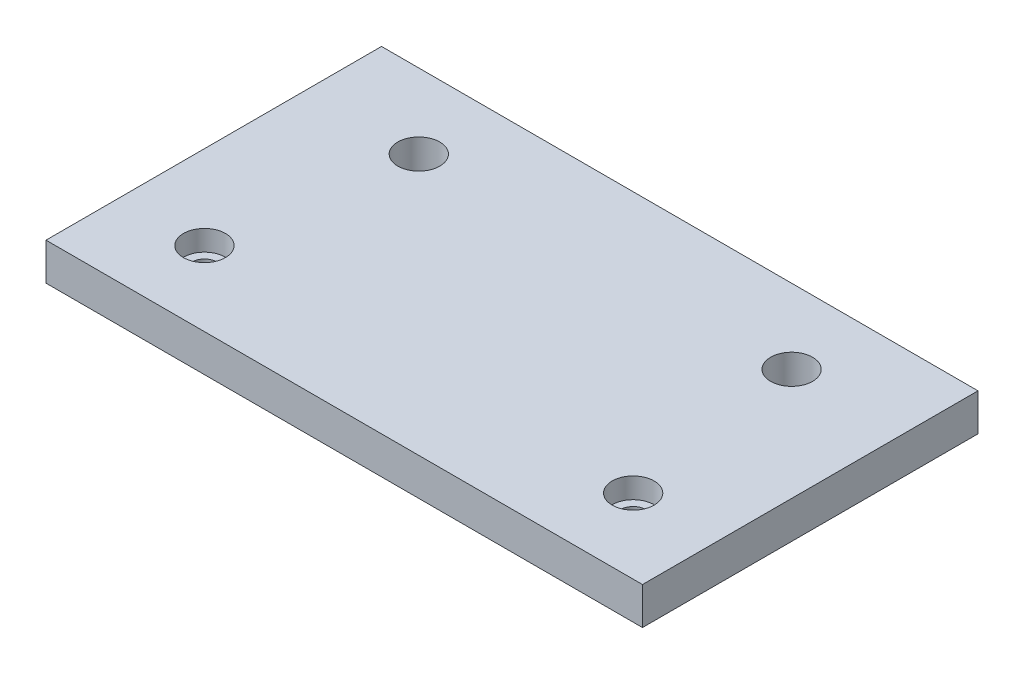
SolidWorks part; units mm, degrees
material "6061 Alloy"
ref_plane "Front Plane" through (0, 0, 0) normal (0, 0, 1) x (1, 0, 0)
ref_plane "Top Plane" through (0, 0, 0) normal (0, 1, 0) x (1, 0, 0)
ref_plane "Right Plane" through (0, 0, 0) normal (1, 0, 0) x (0, 0, -1)
sketch "Sketch1" plane through (0, 0, 0) normal (0, 1, 0) x (1, 0, 0)
  line L1 (0, 0) -> (101.6, 0)
  line L2 (0, 0) -> (0, -57.15)
  line L3 (0, -57.15) -> (101.6, -57.15)
  line L4 (101.6, 0) -> (101.6, -57.15)
  dimension "D1" = 101.6
  dimension "D2" = 57.15
extrude "Boss-Extrude1" add sketch "Sketch1" along normal blind 6.35
sketch "Sketch2" plane through (0, 6.35, 0) normal (0, 1, 0) x (1, 0, 0)
  line L0 (50.8, 0) -> (50.8, -57.15) construction
  line L1 (101.6, 0) -> (0, 0) construction
  line L2 (0, -57.15) -> (101.6, -57.15) construction
  line L3 (0, -28.575) -> (101.6, -28.575) construction
  line L4 (0, 0) -> (0, -57.15) construction
  line L5 (101.6, -57.15) -> (101.6, 0) construction
  point P12 (14.2875, -44.45)
  point P13 (87.3125, -44.45)
  point P14 (19.05, -12.7)
  point P15 (82.55, -12.7)
  dimension "D1" = 36.5125
  dimension "D2" = 12.7
  dimension "D3" = 31.75
  dimension "D4" = 31.75
hole_wizard "CBORE for #6 Socket Head Cap Screw1" positions "Sketch3" profile "Sketch4" counterbore size "#6" standard "ANSI Inch" end condition up to next
sketch "Sketch3" plane through (0, 6.35, 0) normal (0, 1, 0) x (1, 0, 0)
  point P0 (14.2875, -44.45)
  point P3 (87.3125, -44.45)
sketch "Sketch4" plane through (14.2875, 6.35, 44.45) normal (1, 0, 0) x (0, 0, 1)
  line L0 (0, 0) -> (0, 6.35)
  line L1 (0, 6.35) -> (2.1526, 6.35)
  line L3 (2.1526, 6.35) -> (2.1526, 3.5052)
  line L4 (2.1526, 3.5052) -> (3.5725, 3.5052)
  line L5 (3.5725, 3.5052) -> (3.5725, 0)
  line L7 (3.5725, 0) -> (0, 0)
  line L11 (0, -6.35) -> (0, 107.95) construction
  dimension "Thru Hole Dia." = 4.3053
  dimension "Thru Hole Depth" = 6.35
  dimension "C'Bore Dia." = 7.145
  dimension "C'Bore Depth" = 3.5052
hole_wizard "1/4 Clearance Hole1" positions "Sketch5" profile "Sketch6" hole size "1/4" standard "ANSI Inch" end condition up to next
sketch "Sketch5" plane through (0, 6.35, 0) normal (0, 1, 0) x (1, 0, 0)
  point P0 (19.05, -12.7)
  point P3 (82.55, -12.7)
sketch "Sketch6" plane through (19.05, 6.35, 12.7) normal (1, 0, 0) x (0, 0, 1)
  line L0 (0, 0) -> (0, 6.35)
  line L1 (0, 6.35) -> (3.5712, 6.35)
  line L2 (3.5712, 6.35) -> (3.5712, 0)
  line L5 (3.5712, 0) -> (0, 0)
  line L11 (0, -6.35) -> (0, 107.95) construction
  dimension "Thru Hole Dia." = 7.1425
  dimension "Thru Hole Depth" = 6.35
